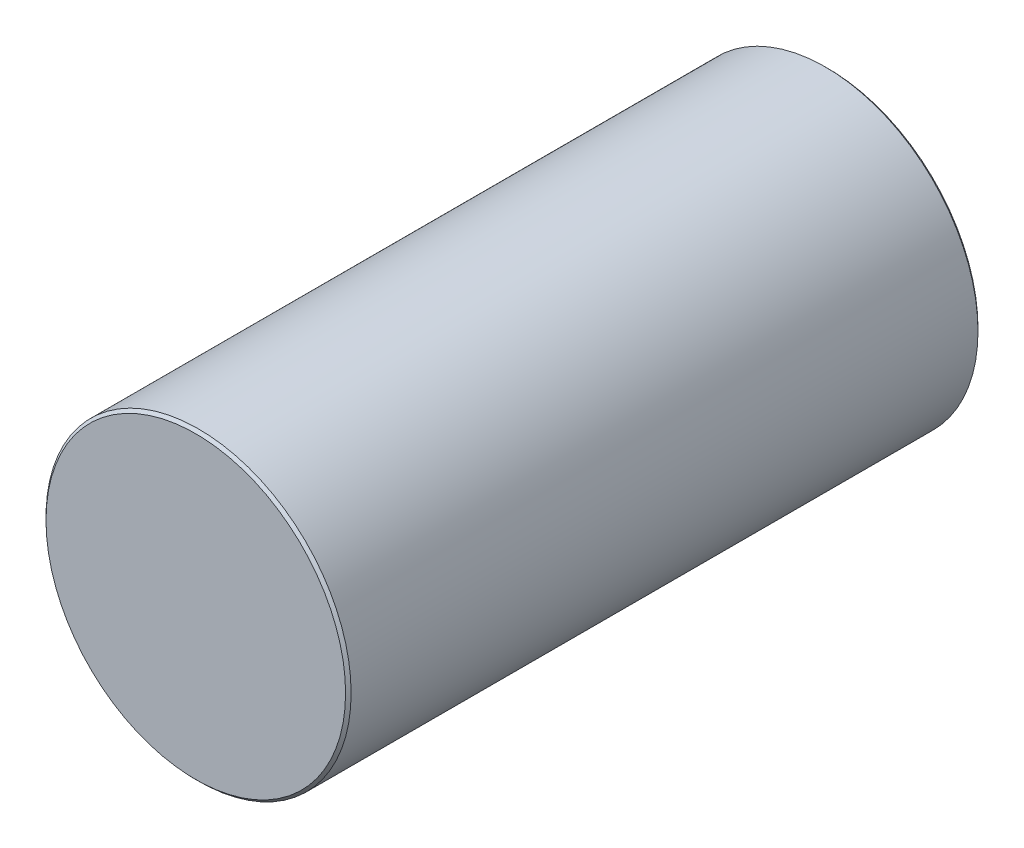
SolidWorks part; units mm, degrees
ref_plane "Front Plane" through (0, 0, 0) normal (0, 0, 1) x (1, 0, 0)
ref_plane "Top Plane" through (0, 0, 0) normal (0, 1, 0) x (1, 0, 0)
ref_plane "Right Plane" through (0, 0, 0) normal (1, 0, 0) x (0, 0, -1)
sketch "Sketch2" plane through (0, 0, 0) normal (0, 0, 1) x (1, 0, 0)
  circle A0 centre (0, 0) radius 2.75
  dimension "D1" = 5.5
extrude "Boss-Extrude1" add sketch "Sketch2" along normal blind 11.4
chamfer "Chamfer2" distance 0.05 angle 45 2 edges at (2.75, 0, 11.4) (2.75, 0, 0)
